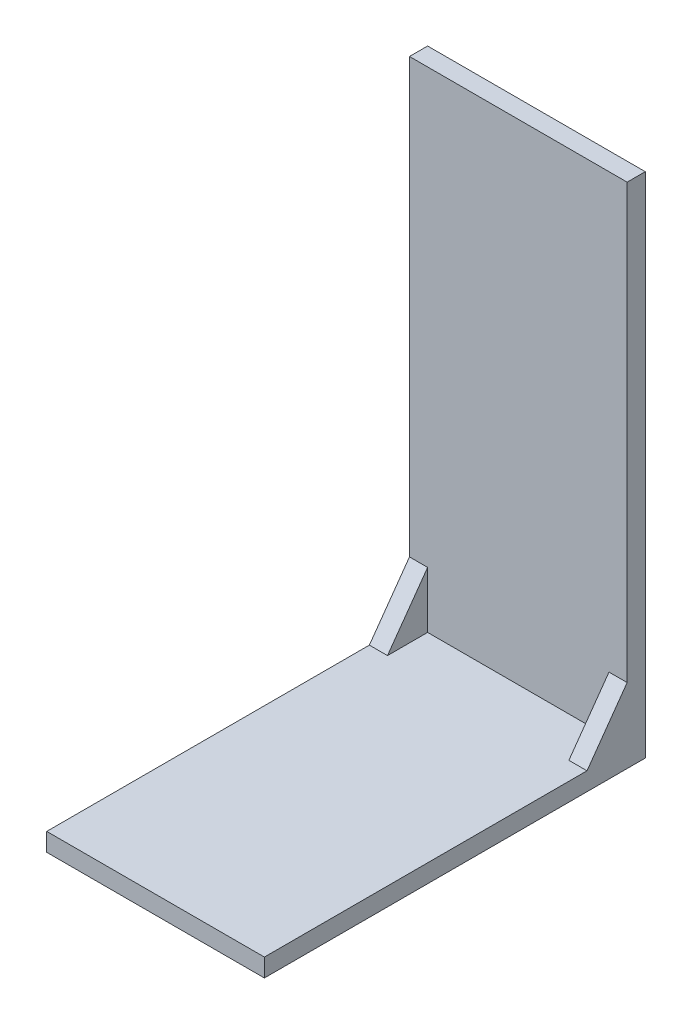
SolidWorks part; units mm, degrees
material "Plain Carbon Steel"
ref_plane "Front Plane" through (0, 0, 0) normal (0, 0, 1) x (1, 0, 0)
ref_plane "Top Plane" through (0, 0, 0) normal (0, 1, 0) x (1, 0, 0)
ref_plane "Right Plane" through (0, 0, 0) normal (1, 0, 0) x (0, 0, -1)
sketch "Sketch1" plane through (0, 0, 0) normal (0, 0, 1) x (1, 0, 0)
  line L1 (0, 0) -> (76.2, 0)
  line L2 (0, 0) -> (0, 177.8)
  line L3 (0, 177.8) -> (76.2, 177.8)
  line L4 (76.2, 0) -> (76.2, 177.8)
  dimension "D1" = 177.8
  dimension "D2" = 76.2
extrude "Rise" add sketch "Sketch1" along normal blind 6.35
sketch "Sketch2" plane through (0, 0, 6.35) normal (0, 0, 1) x (1, 0, 0)
  line L0 (76.2, 0) -> (76.2, 177.8) construction
  line L1 (0, 0) -> (76.2, 0)
  line L2 (0, 0) -> (0, 6.35)
  line L3 (0, 6.35) -> (76.2, 6.35)
  line L4 (76.2, 0) -> (76.2, 6.35)
  dimension "D1" = 6.35
extrude "Base" add sketch "Sketch2" along normal blind 127
sketch "Sketch4" plane through (76.2, 0, 0) normal (1, 0, 0) x (0, 0, -1)
  line L0 (-6.35, 26.0726) -> (-6.35, 6.35)
  line L1 (-6.35, 6.35) -> (-6.35, 177.8) construction
  line L2 (-6.35, 6.35) -> (-20.4002, 6.35)
  line L3 (-133.35, 6.35) -> (-6.35, 6.35) construction
  line L4 (-20.4002, 6.35) -> (-6.35, 26.0726)
extrude "Rib" add sketch "Sketch4" against normal blind 6.35
ref_plane "Plane1" through (38.1, 0, 0) normal (-1, 0, 0) x (0, 0, 1)
mirror "RibCopy" about plane through (38.1, 0, 0) normal (-1, 0, 0) of "Rib"
